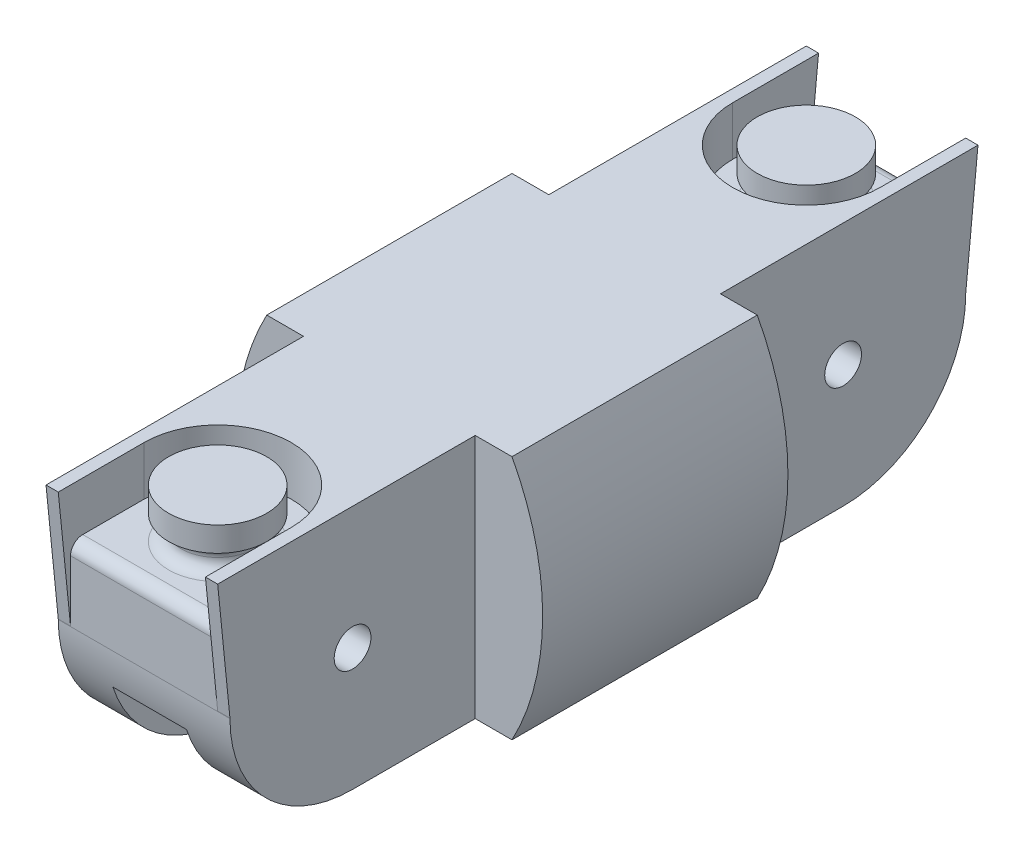
SolidWorks part; units mm, degrees
ref_plane "Alzado" through (0, 0, 0) normal (0, 0, 1) x (1, 0, 0)
ref_plane "Planta" through (0, 0, 0) normal (0, 1, 0) x (1, 0, 0)
ref_plane "Vista lateral" through (0, 0, 0) normal (1, 0, 0) x (0, 0, -1)
sketch "Croquis1" plane through (0, 0, 0) normal (0, 0, 1) x (1, 0, 0)
  line L1 (-10, 10) -> (10, 10)
  line L3 (-10, -10) -> (10, -10)
  line L5 (-10.6997, 8.5598) -> (10.6997, -8.5598) construction
  line L6 (-10.6997, -8.5598) -> (10.6997, 8.5598) construction
  arc A0 (-10, 10) -> (-10, -10) centre (8.75, 0) ccw
  arc A1 (10, -10) -> (10, 10) centre (-8.75, 0) ccw
  point P0 (0, 0)
  point P4 (12.5, 0)
  point P13 (-12.5, 0)
  dimension "D1" = 20
  dimension "D2" = 25
  dimension "D3" = 20
extrude "Saliente-Extruir1" add sketch "Croquis1" along normal blind 20
sketch "Croquis5" plane through (0, 0, 0) normal (0, 0, -1) x (-1, 0, 0)
  line L0 (10, -10) -> (-10, -10) construction
  circle A0 centre (0, -7) radius 1.5
  dimension "D2" = 3
  dimension "D1" = 3
extrude "Cortar-Extruir3" cut sketch "Croquis5" against normal blind 20
sketch "Croquis2" plane through (0, 0, 0) normal (0, 0, -1) x (-1, 0, 0)
  line L0 (10, -10) -> (-10, -10) construction
  line L2 (-7, 10) -> (-7, -10)
  line L3 (-7, -10) -> (-3, -10)
  line L4 (7, 10) -> (7, -10)
  line L5 (-7, 10) -> (7, -10) construction
  line L6 (-7, -10) -> (7, 10) construction
  line L8 (3, -3) -> (3, -10)
  line L10 (3, -10) -> (7, -10)
  line L11 (-3, -3) -> (3, -3)
  line L12 (-7, 10) -> (7, 10)
  line L13 (-3, -3) -> (-3, -10)
  point P0 (0, 0)
  dimension "D1" = 14
  dimension "D3" = 4
  dimension "D4" = 7
extrude "Saliente-Extruir2" add sketch "Croquis2" along normal blind 20
sketch "Croquis3" plane through (0, 0, 20) normal (0, 0, 1) x (1, 0, 0)
  line L0 (-10, -10) -> (10, -10) construction
  line L2 (-7, 10) -> (-7, -10)
  line L3 (-7, -10) -> (-3, -10)
  line L4 (7, 10) -> (7, -10)
  line L5 (-7, 10) -> (7, -10) construction
  line L6 (-7, -10) -> (7, 10) construction
  line L8 (3, -3) -> (3, -10)
  line L9 (3, -10) -> (7, -10)
  line L11 (-3, -3) -> (3, -3)
  line L12 (-3, -3) -> (-3, -10)
  line L13 (-7, 10) -> (7, 10)
  point P0 (0, 0)
  dimension "D1" = 14
  dimension "D3" = 4
  dimension "D4" = 7
extrude "Saliente-Extruir3" add sketch "Croquis3" along normal blind 20
sketch "Croquis4" plane through (-7, 0, 0) normal (-1, 0, 0) x (0, 0, 1)
  line L1 (-20, -10) -> (-20, 10) construction
  line L3 (40, 10) -> (40, -10) construction
  line L4 (-20, -10) -> (0, -10) construction
  line L5 (40, -10) -> (20, -10) construction
  circle A0 centre (-10, 0) radius 1.5
  circle A1 centre (30, 0) radius 1.5
  dimension "D3" = 3
  dimension "D6" = 3
  dimension "D1" = 10
  dimension "D2" = 10
  dimension "D4" = 10
  dimension "D5" = 10
extrude "Cortar-Extruir2" cut sketch "Croquis4" against normal blind 14
fillet "Redondeo1" radius 10 4 edges at (5, -10, 40) (-5, -10, 40) (5, -10, -20) (-5, -10, -20)
sketch "Sketch1" plane through (0, 10, 0) normal (0, 1, 0) x (1, 0, 0)
  line L0 (-7, 20) -> (7, 20) construction
  line L1 (7, -40) -> (-7, -40) construction
  line L4 (-6, 14) -> (-6, 20)
  line L5 (-6, 20) -> (6, 20)
  line L6 (6, 14) -> (6, 20)
  line L8 (-6, -34) -> (-6, -40)
  line L9 (-6, -40) -> (6, -40)
  line L10 (6, -34) -> (6, -40)
  arc A0 (-6, 14) -> (6, 14) centre (0, 14) ccw
  arc A1 (6, -34) -> (-6, -34) centre (0, -34) ccw
  dimension "D1" = 12
  dimension "D3" = 12
  dimension "D2" = 6
  dimension "D4" = 6
extrude "Cut-Extrude1" cut sketch "Sketch1" against normal blind 4
sketch "Sketch2" plane through (0, 6, 0) normal (0, 1, 0) x (1, 0, 0)
  circle A0 centre (0, -34) radius 3
  circle A1 centre (0, 14) radius 3
  dimension "D1" = 6
  dimension "D2" = 6
extrude "Boss-Extrude1" add sketch "Sketch2" along normal blind 2
sketch "Sketch3" plane through (0, 8, 0) normal (0, 1, 0) x (1, 0, 0)
  circle A0 centre (0, -34) radius 4
  circle A1 centre (0, 14) radius 4
  dimension "D1" = 8
  dimension "D2" = 8
extrude "Boss-Extrude2" add sketch "Sketch3" along normal blind 2
fillet "Fillet1" radius 1 4 edges at (0, 8, 37) (0, 6, 37) (0, 8, -11) (0, 6, -11)
fillet "Fillet2" radius 1 2 edges at (0, 6, 40) (0, 6, -20)
fillet "Fillet3" radius 1 2 edges at (-1.5, -7, 20) (-1.5, -7, 0)
sketch "Sketch5" plane through (7, 0, 0) normal (1, 0, 0) x (0, 0, -1)
  line L0 (20, 10) -> (21, 10)
  line L1 (-40, 10) -> (-41, 10)
  line L2 (-41, 10) -> (-39.7942, -2.0184)
  line L3 (-39.7942, -2.0184) -> (-40, 10)
  line L4 (21, 10) -> (19.7942, -2.0184)
  line L5 (19.7942, -2.0184) -> (20, 10)
  arc A0 (-40, 0) -> (-30, -10) centre (-30, 0) ccw construction
  arc A1 (10, -10) -> (20, 0) centre (10, 0) ccw construction
  dimension "D1" = 1
  dimension "D2" = 1
sketch "Sketch6" plane through (-7, 0, 0) normal (-1, 0, 0) x (0, 0, 1)
  line L0 (-20, 10) -> (-21, 10)
  line L1 (-21, 10) -> (-19.7942, -2.0184)
  line L2 (-19.7942, -2.0184) -> (-20, 10)
  line L3 (40, 10) -> (41, 10)
  line L4 (41, 10) -> (39.7942, -2.0184)
  line L5 (39.7942, -2.0184) -> (40, 10)
extrude "Boss-Extrude3" add sketch "Sketch5" against normal blind 1
extrude "Boss-Extrude4" add sketch "Sketch6" against normal blind 1
